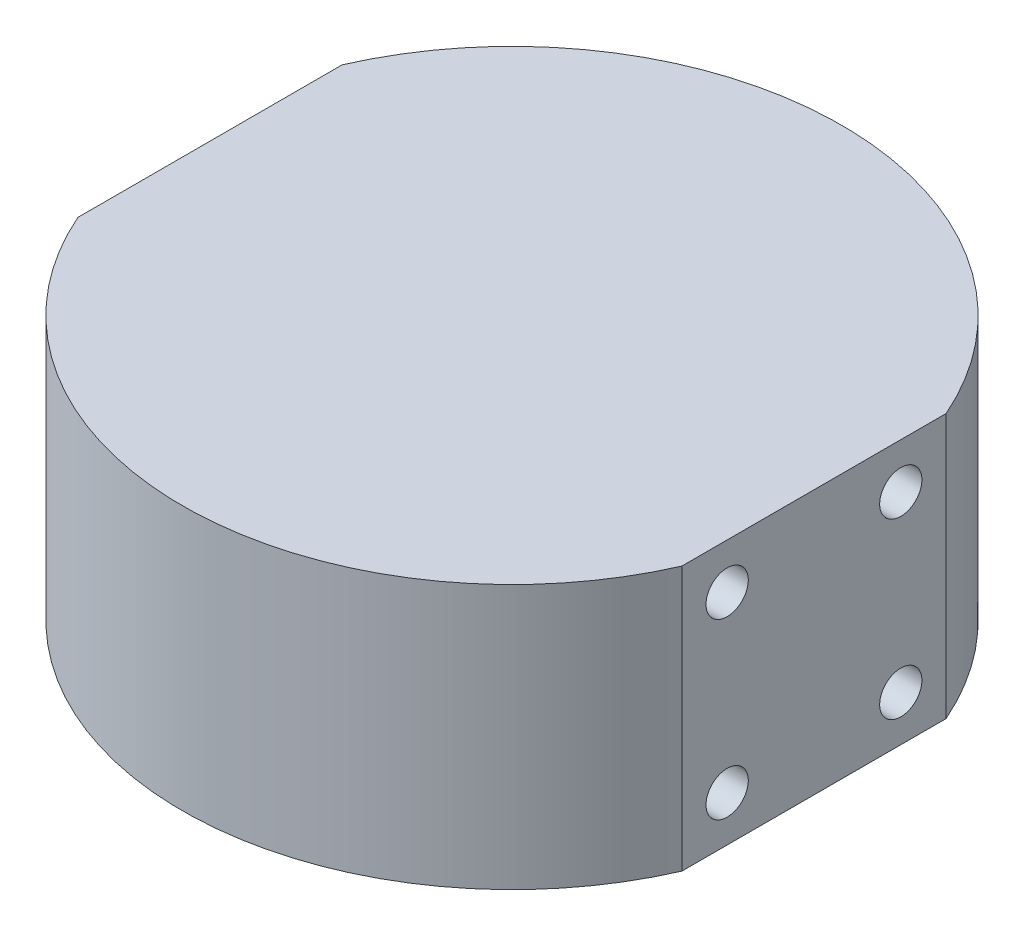
SolidWorks part; units mm, degrees
ref_plane "Front Plane" through (0, 0, 0) normal (0, 0, 1) x (1, 0, 0)
ref_plane "Top Plane" through (0, 0, 0) normal (0, 1, 0) x (1, 0, 0)
ref_plane "Right Plane" through (0, 0, 0) normal (1, 0, 0) x (0, 0, -1)
sketch "Sketch1" plane through (0, 0, 0) normal (0, 1, 0) x (1, 0, 0)
  line L0 (-40, 17.5) -> (-40, -17.5)
  line L1 (40, 17.5) -> (40, -17.5)
  arc A0 (-40, -17.5) -> (40, -17.5) centre (0, 0) ccw
  arc A1 (40, 17.5) -> (-40, 17.5) centre (0, 0) ccw
  point P7 (-40, 0)
  dimension "D1" = 40
  dimension "D2" = 35
extrude "Boss-Extrude1" add sketch "Sketch1" along normal blind 35
sketch "Sketch2" plane through (-40, 0, 0) normal (-1, 0, 0) x (0, 0, 1)
  line L0 (0, 0) -> (0, 35) construction
  line L1 (-17.5, 35) -> (17.5, 35) construction
  line L2 (-17.5, 17.5) -> (17.5, 17.5) construction
  line L3 (-17.5, 35) -> (-17.5, 0) construction
  line L4 (17.5, 35) -> (17.5, 0) construction
  circle A0 centre (-11.5, 29) radius 2.8
  circle A1 centre (11.5, 29) radius 2.8
  circle A2 centre (-11.5, 6) radius 2.8
  circle A3 centre (11.5, 6) radius 2.8
  dimension "D1" = 5.6
  dimension "D2" = 23
  dimension "D3" = 23
extrude "Cut-Extrude1" cut sketch "Sketch2" against normal blind 10
extrude "Cut-Extrude2" cut sketch "Sketch2<2>" along normal blind 10 from surface starting at face at (40, 17.5, 0)
sketch "Sketch2<2>" plane through (-40, 0, 0) normal (-1, 0, 0) x (0, 0, 1) same geometry as "Sketch2"
